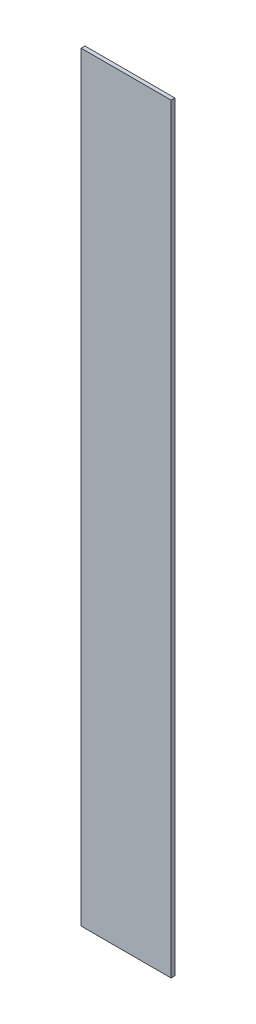
SolidWorks part; units mm, degrees
material "Teak"
ref_plane "Front Plane" through (0, 0, 0) normal (0, 0, 1) x (1, 0, 0)
ref_plane "Top Plane" through (0, 0, 0) normal (0, 1, 0) x (1, 0, 0)
ref_plane "Right Plane" through (0, 0, 0) normal (1, 0, 0) x (0, 0, -1)
sketch "Sketch1" plane through (0, 0, 0) normal (0, 0, 1) x (1, 0, 0)
  line L1 (-37.525, -317.5) -> (37.525, -317.5)
  line L2 (-37.525, -317.5) -> (-37.525, 317.5)
  line L3 (-37.525, 317.5) -> (37.525, 317.5)
  line L4 (37.525, -317.5) -> (37.525, 317.5)
  line L5 (-37.525, -317.5) -> (37.525, 317.5) construction
  line L6 (-37.525, 317.5) -> (37.525, -317.5) construction
  point P0 (0, 0)
  dimension "D1" = 75.05
  dimension "D2" = 635
extrude "Boss-Extrude1" add sketch "Sketch1" along normal blind 3.175
